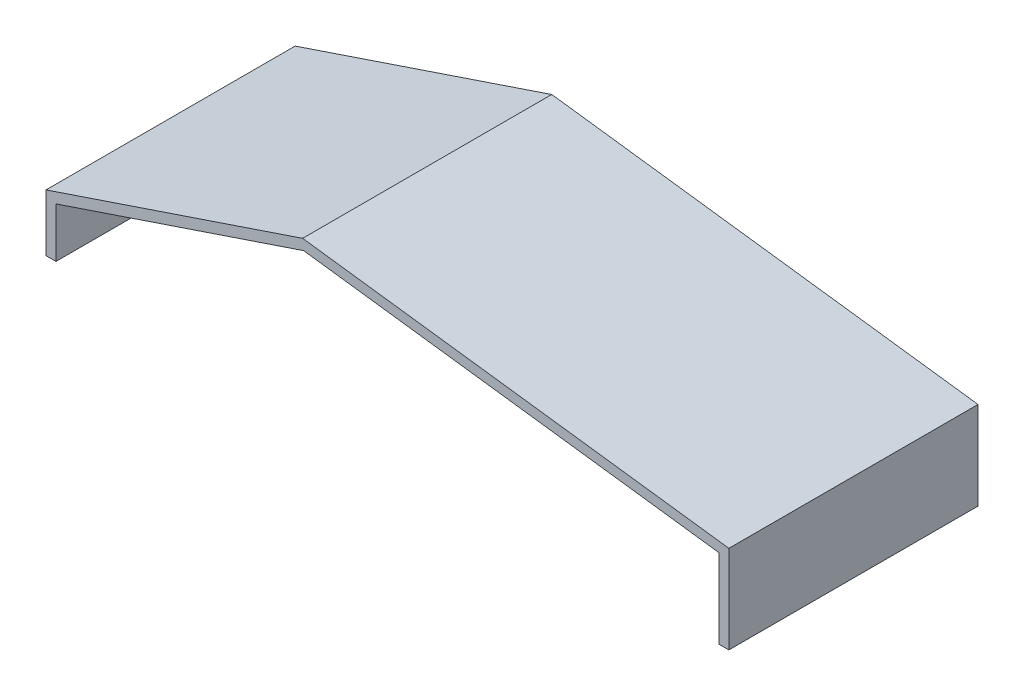
SolidWorks part; units mm, degrees
ref_plane "Front Plane" through (0, 0, 0) normal (0, 0, 1) x (1, 0, 0)
ref_plane "Top Plane" through (0, 0, 0) normal (0, 1, 0) x (1, 0, 0)
ref_plane "Right Plane" through (0, 0, 0) normal (1, 0, 0) x (0, 0, -1)
sketch "Sketch1" plane through (0, 0, 0) normal (0, 0, 1) x (1, 0, 0)
  line L0 (0, 0) -> (100, 4.5452) construction
  line L1 (100, 4.5452) -> (37.5814, 12.6493)
  line L2 (37.5814, 12.6493) -> (0, 0)
  line L3 (37.381, 14.6921) -> (-14.1253, -2.6441)
  line L4 (-14.1253, -2.6441) -> (111.4217, 3.0622) construction
  line L5 (122.9273, 3.5852) -> (37.381, 14.6921)
  line L6 (-14.1253, -2.6441) -> (122.9273, -2.6441) construction
  line L7 (-14.1253, -2.6441) -> (-14.1253, -14.0812)
  line L8 (122.9273, -2.6441) -> (122.9273, -14.0812)
  line L9 (122.9273, 3.5852) -> (122.9273, -2.6441) construction
  line L11 (120.9273, -2.6441) -> (120.9273, -14.0812)
  line L13 (122.9273, -2.6441) -> (122.9273, 3.5852)
  line L14 (-14.1253, -14.0812) -> (-12.1253, -14.0812)
  line L15 (120.9273, -14.0812) -> (122.9273, -14.0812)
  line L17 (-14.1253, -2.6441) -> (122.9273, 3.5852) construction
  line L18 (100, 4.5452) -> (120.9273, 1.8281)
  line L19 (120.9273, 1.8281) -> (120.9273, -2.6441)
  line L20 (0, 0) -> (-12.1253, -4.0812)
  line L21 (-12.1253, -4.0812) -> (-12.1253, -14.0812)
  point P3 (120.9273, -2.6733)
  dimension "D1" = 100
  dimension "D2" = 16
  dimension "D3" = 10
  dimension "D4" = 2
  dimension "D5" = 137.0526
  dimension "D6" = 2
  dimension "D7" = 2
  dimension "D8" = 10
extrude "Boss-Extrude2" add sketch "Sketch1" along normal blind 50
